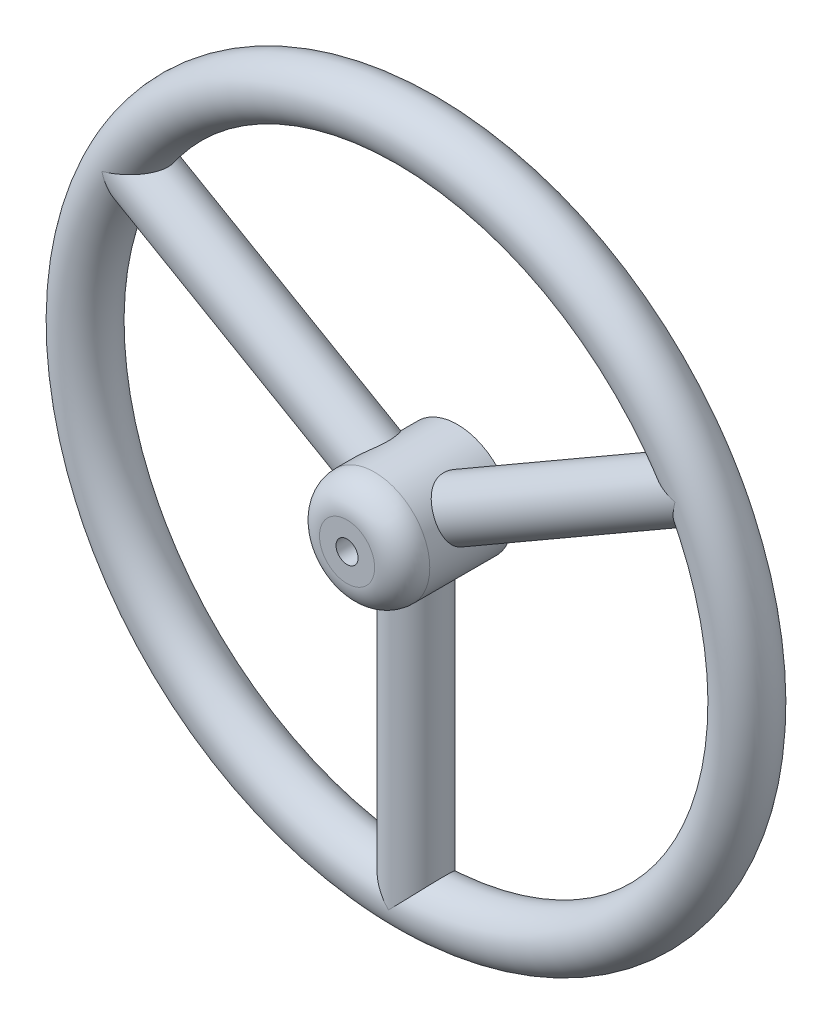
SolidWorks part; units mm, degrees
ref_plane "Front Plane" through (0, 0, 0) normal (0, 0, 1) x (1, 0, 0)
ref_plane "Top Plane" through (0, 0, 0) normal (0, 1, 0) x (1, 0, 0)
ref_plane "Right Plane" through (0, 0, 0) normal (1, 0, 0) x (0, 0, -1)
sketch "Sketch6" plane through (0, 0, 0) normal (0, 1, 0) x (1, 0, 0)
  line L0 (0, 0) -> (0, 73) construction
  circle A0 centre (120, 0) radius 10
  dimension "D1" = 20
  dimension "D2" = 120
  dimension "D3" = 73
revolve "Revolve1" add sketch "Sketch6" angle 360 about L0
sketch "Sketch7" plane through (0, 0, 0) normal (0, 0, 1) x (1, 0, 0)
  circle A0 centre (0, 0) radius 20
  circle A1 centre (0, 0) radius 8
  dimension "D2" = 16
  dimension "D1" = 40
extrude "Boss-Extrude1" add sketch "Sketch7" along normal mid plane 30 separate body
ref_plane "Plane1" through (0, -65, 0) normal (0, 1, 0) x (1, 0, 0)
sketch "Sketch8" plane through (0, -65, 0) normal (0, 1, 0) x (1, 0, 0)
  circle A0 centre (0, 0) radius 10
  circle A1 centre (0, 0) radius 6
  dimension "D1" = 12
  dimension "D2" = 20
extrude "Boss-Extrude3" add sketch "Sketch8" against normal up to next
sketch "Sketch10" plane through (0, 0, 15) normal (0, 0, 1) x (1, 0, 0)
  line L1 (-9.2683, 1.39) -> (-7.8783, 1.39)
  line L2 (-9.2683, 1.39) -> (-9.2683, -1.39)
  line L3 (-9.2683, -1.39) -> (-7.8783, -1.39)
  arc A1 (-7.8783, 1.39) -> (-7.8783, -1.39) centre (0, 0) ccw
  circle A3 centre (0, 0) radius 8 construction
  dimension "D2" = 1.39
  dimension "D1" = 2.78
extrude "Cut-Extrude1" cut sketch "Sketch10" against normal through all
pattern_circular "CirPattern2" count 3 over 360 about axis through (0, 0, 15) along (0, 0, -1) of "Boss-Extrude3"
sketch "Sketch11" plane through (0, -65, 0) normal (0, 1, 0) x (1, 0, 0)
  circle A0 centre (0, 0) radius 6
  circle A1 centre (0, 0) radius 10
  circle A2 centre (0, 0) radius 10 construction
  circle A3 centre (0, 0) radius 6 construction
extrude "Boss-Extrude4" add sketch "Sketch11" along normal up to surface (45 mm away) up to face at (20, 0, 15)
sketch "Sketch12" plane through (-56.2917, 32.5, 0) normal (0.866, -0.5, 0) x (0, 0, -1)
  circle A0 centre (0, 0) radius 6
  circle A1 centre (0, 0) radius 10
  circle A2 centre (0, 0) radius 6 construction
  circle A3 centre (0, 0) radius 10 construction
extrude "Boss-Extrude5" add sketch "Sketch12" along normal up to next
sketch "Sketch13" plane through (56.2917, 32.5, 0) normal (-0.866, -0.5, 0) x (0, 0, 1)
  circle A0 centre (0, 0) radius 6
  circle A1 centre (0, 0) radius 10
  circle A2 centre (0, 0) radius 6 construction
  circle A3 centre (0, 0) radius 10 construction
extrude "Boss-Extrude6" add sketch "Sketch13" along normal up to next
sketch "Sketch14" plane through (0, 0, 15) normal (0, 0, 1) x (1, 0, 0)
  circle A0 centre (0, 0) radius 20
  circle A1 centre (0, 0) radius 4
  circle A2 centre (0, 0) radius 20 construction
  dimension "D1" = 8
extrude "Boss-Extrude7" add sketch "Sketch14" along normal blind 10
fillet "Fillet1" radius 10 1 edges at (20, 0, 25)
equation "\"D2@Sketch10\" = \"keyway_height\""
equation "\"D1@Sketch10\"=\"keyway_width\""
equation "\"D1@Boss-Extrude1\"=\"keyway_length\""
equation "\"shaft inner diameter\"= 15mm "
equation "\"shaft outer diameter\"= 20mm "
equation "\"column angle\" = 45deg "
equation "\"short_bearing_outer_width\" = 10mm "
equation "\"wheel base\" = 1561mm "
equation "\"track\" = 1354mm "
equation "\"turning radius\" = 2000mm "
equation "\"turn to lock\" = 0.75mm "
equation "\"steering arm length\" = 100mm "
equation "\"primary shaft small diameter\" = 16mm "
equation "\"primary shaft large diameter\" = 24mm "
equation "\"secondary shaft small diameter\" = 16mm "
equation "\"secondary shaft large diameter\" = 25mm "
equation "\"steering column length\" = 555mm "
equation "\"keyway_height\" = 1.39mm "
equation "\"keyway_width\" = 2.78mm "
equation "\"keyway_length\" = 30mm "
equation "\"steering wheel bolt width\" = 6mm "
equation "\"steering wheel bolt length\" = 40mm "
equation "\"bushing length\" = 40mm "
equation "\"bushing thickness\" = 3mm "
equation "\"u_joint clearance\" = 30mm "
equation "\"u_joint thickness\" = 7.5mm "
equation "\"horizontal shaft length\" = 90mm "
equation "\"column bushing diameter\" = \"primary shaft small diameter\" + 4 "
equation "\"column bushing distance\" = \"steering column length\"/4 "
equation "\"pinion width\" = 26.5mm "
equation "\"pin hole diameter\" = 10mm "
equation "\"rack hole to hole\" = 500mm "
equation "\"rack length\" = \"rack hole to hole\" + \"pin hole diameter\"*2 "
equation "\"max turning angle\" = atn(\"wheel base\" / (\"turning radius\" - 0.5 * \"track\")) "
equation "\"max travel\" = 2 * \"steering arm length\" * sin(0.5 * \"max turning angle\") "
equation "\"pitch diameter\" = \"max travel\"/(pi * \"turn to lock\") "
equation "\"number of teeth\" = 18mm "
equation "\"pressure angle\" = 20deg "
equation "\"module\" = \"pitch diameter\" / \"number of teeth\" "
equation "\"tie rod length\" = 305mm "
equation "\"tie rod inner diameter\" = 6.6mm "
equation "\"tie rod outer diameter\" = 8.1mm "
equation "\"D1@Sketch14\"=\"steering wheel bolt width\"+2"
equation "\"D2@Sketch7\"=\"primary shaft small diameter\""
